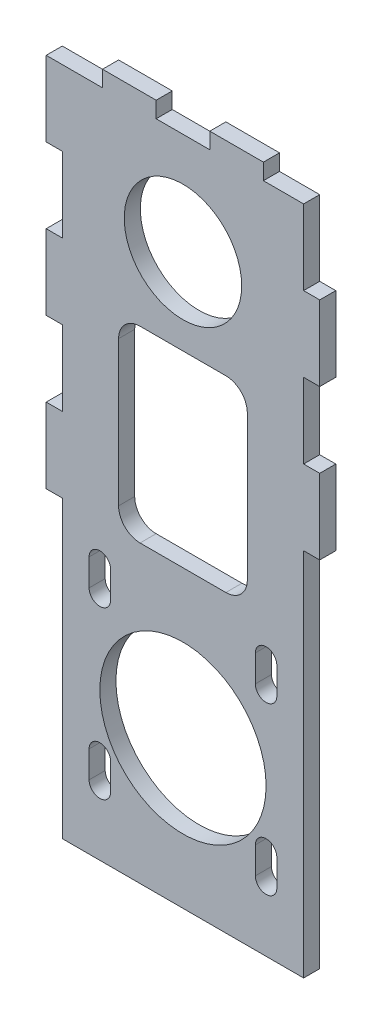
SolidWorks part; units mm, degrees
ref_plane "Front Plane" through (0, 0, 0) normal (0, 0, 1) x (1, 0, 0)
ref_plane "Top Plane" through (0, 0, 0) normal (0, 1, 0) x (1, 0, 0)
ref_plane "Right Plane" through (0, 0, 0) normal (1, 0, 0) x (0, 0, -1)
sketch "Sketch1" plane through (0, 0, 0) normal (0, 0, 1) x (1, 0, 0)
  line L1 (-22.5, -35) -> (22.5, -35)
  line L2 (-22.5, -35) -> (-22.5, 35)
  line L3 (-22.5, 35) -> (22.5, 35)
  line L4 (22.5, -35) -> (22.5, 35)
  line L5 (-22.5, -35) -> (22.5, 35) construction
  line L6 (-22.5, 35) -> (22.5, -35) construction
  point P0 (0, 0)
  dimension "D1" = 70
  dimension "D2" = 45
extrude "Boss-Extrude1" add sketch "Sketch1" along normal blind 3 contours L2 L3 L4 L1
sketch "Sketch2" plane through (0, 0, 3) normal (0, 0, 1) x (1, 0, 0)
  line L0 (-22.5, -35) -> (22.5, -35) construction
  line L1 (-12, 0) -> (12, 0)
  line L2 (-12, 0) -> (-12, -35)
  line L3 (-12, -35) -> (12, -35)
  line L4 (12, 0) -> (12, -35)
  line L5 (-12, 0) -> (12, -35) construction
  line L6 (-12, -35) -> (12, 0) construction
  circle A0 centre (0, 16) radius 10.95
  point P2 (0, -17.5)
  dimension "D1" = 21.9
  dimension "D2" = 16
  dimension "D3" = 24
  dimension "D4" = 35
extrude "Cut-Extrude1" cut sketch "Sketch2" against normal through all
sketch "Sketch4" plane through (0, 0, 3) normal (0, 0, 1) x (1, 0, 0)
  line L0 (0, 35) -> (0, 41.52) construction
  line L1 (-15, 35) -> (-5, 35)
  line L2 (-15, 35) -> (-15, 38)
  line L3 (-15, 38) -> (-5, 38)
  line L4 (-5, 35) -> (-5, 38)
  line L5 (-22.5, 35) -> (22.5, 35) construction
  line L6 (5, 35) -> (5, 38)
  line L7 (15, 38) -> (5, 38)
  line L8 (15, 35) -> (15, 38)
  line L9 (15, 35) -> (5, 35)
  dimension "D1" = 3
  dimension "D2" = 10
  dimension "D3" = 10
extrude "Boss-Extrude3" add sketch "Sketch4" against normal up to surface (3 mm away) up to face at (0, -8.75, 0)
sketch "Sketch3" plane through (0, 0, 0) normal (0, 0, -1) x (-1, 0, 0)
  line L0 (22.5, 7) -> (22.5, -7)
  line L1 (22.5, 35) -> (25.5, 35)
  line L2 (22.5, 35) -> (22.5, 21)
  line L3 (22.5, 21) -> (25.5, 21)
  line L4 (25.5, 35) -> (25.5, 21)
  line L5 (22.5, 7) -> (25.5, 7)
  line L6 (25.5, 7) -> (25.5, -7)
  line L7 (22.5, -7) -> (25.5, -7)
  line L8 (22.5, -21) -> (22.5, -35)
  line L9 (22.5, -21) -> (25.5, -21)
  line L10 (25.5, -21) -> (25.5, -35)
  line L11 (22.5, -35) -> (25.5, -35)
  line L12 (22.5, -35) -> (22.5, 35) construction
  line L13 (-22.5, -35) -> (-22.5, 35) construction
  line L14 (-22.5, 21) -> (-25.5, 21)
  line L15 (-22.5, 21) -> (-22.5, 7)
  line L16 (-22.5, 7) -> (-25.5, 7)
  line L17 (-25.5, 21) -> (-25.5, 7)
  line L18 (22.5, -35) -> (12, -35) construction
  line L19 (-22.5, -7) -> (-25.5, -7)
  line L20 (-22.5, -7) -> (-22.5, -21)
  line L21 (-22.5, -21) -> (-25.5, -21)
  line L22 (-25.5, -7) -> (-25.5, -21)
  dimension "D1" = 3
  dimension "D2" = 14
  dimension "D3" = 3
extrude "Boss-Extrude2" add sketch "Sketch3" against normal up to surface (3 mm away) up to face at (-0.7813, 13.875, 3)
sketch "Sketch5" plane through (0, 0, 3) normal (0, 0, 1) x (1, 0, 0)
  line L0 (-22.5, -21) -> (-22.5, -7) construction
  line L1 (22.5, -35) -> (-22.5, -35)
  line L2 (22.5, -35) -> (22.5, -90)
  line L3 (22.5, -90) -> (-22.5, -90)
  line L4 (-22.5, -35) -> (-22.5, -90)
  dimension "D1" = 55
extrude "Boss-Extrude4" add sketch "Sketch5" against normal up to surface (3 mm away) up to face at (-0.5781, 5.8437, 0)
fillet "Fillet1" radius 4 4 edges at (12, 0, 1.5) (-12, 0, 1.5) (12, -35, 1.5) (-12, -35, 1.5)
sketch "Sketch6" plane through (0, 0, 0) normal (0, 0, -1) x (-1, 0, 0)
  line L0 (0, -35) -> (0, -90) construction
  line L1 (15.5, -47) -> (-15.5, -47) construction
  line L2 (15.5, -47) -> (15.5, -78) construction
  line L3 (15.5, -78) -> (-15.5, -78) construction
  line L4 (-15.5, -47) -> (-15.5, -78) construction
  line L5 (15.5, -47) -> (-15.5, -78) construction
  line L6 (15.5, -78) -> (-15.5, -47) construction
  line L7 (8, -35) -> (-8, -35) construction
  line L8 (-22.5, -90) -> (22.5, -90) construction
  line L9 (15.5, -78) -> (15.5, -73) construction
  line L10 (13.5, -78) -> (13.5, -73)
  line L11 (17.5, -78) -> (17.5, -73)
  line L12 (-15.5, -78) -> (-15.5, -73) construction
  line L13 (-17.5, -78) -> (-17.5, -73)
  line L14 (-13.5, -78) -> (-13.5, -73)
  line L15 (-15.5, -47) -> (-15.5, -42) construction
  line L16 (-17.5, -47) -> (-17.5, -42)
  line L17 (-13.5, -47) -> (-13.5, -42)
  line L18 (15.5, -47) -> (15.5, -42) construction
  line L19 (13.5, -47) -> (13.5, -42)
  line L20 (17.5, -47) -> (17.5, -42)
  arc A0 (13.5, -78) -> (17.5, -78) centre (15.5, -78) ccw
  arc A1 (17.5, -73) -> (13.5, -73) centre (15.5, -73) ccw
  arc A2 (-17.5, -78) -> (-13.5, -78) centre (-15.5, -78) ccw
  arc A3 (-13.5, -73) -> (-17.5, -73) centre (-15.5, -73) ccw
  arc A4 (-17.5, -47) -> (-13.5, -47) centre (-15.5, -47) ccw
  arc A5 (-13.5, -42) -> (-17.5, -42) centre (-15.5, -42) ccw
  arc A6 (13.5, -47) -> (17.5, -47) centre (15.5, -47) ccw
  arc A7 (17.5, -42) -> (13.5, -42) centre (15.5, -42) ccw
  circle A8 centre (0, -62.5) radius 15.5
  point P0 (0, -62.5)
  point P14 (15.5, -75.5)
  point P19 (-15.5, -75.5)
  point P25 (-15.5, -44.5)
  point P31 (15.5, -44.5)
  dimension "D2" = 2
  dimension "D1" = 31
  dimension "D3" = 5
extrude "Cut-Extrude2" cut sketch "Sketch6" against normal blind 10
equation "\"pulley_pitch_diam\"= 12.73mm"
equation "\"pulley_total_width\"= 16mm"
equation "\"belt_width\"= 6mm"
equation "\"material_thickness\"= 3mm"
equation "\"D1@Boss-Extrude1\"=\"material_thickness\""
equation "\"shaft_diam\"= 8mm"
equation "\"D1@Sketch2\"=\"bearing_od\" - 0.1mm"
equation "\"pulley_total_diam\"= 16mm"
equation "\"D2@Sketch2\"=\"pulley_total_diam\" "
equation "\"D3@Sketch2\"=\"pulley_total_width\" * 1.5"
equation "\"D1@Sketch3\"=\"material_thickness\""
equation "\"bearing_od\"= 22mm"
equation "\"bearing_thickness\"= 7mm"
equation "\"D1@Sketch4\"=\"material_thickness\""
